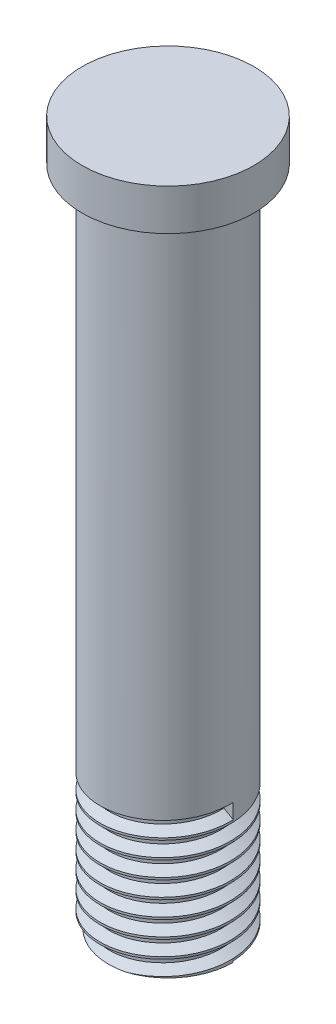
SolidWorks part; units mm, degrees
ref_plane "Front Plane" through (0, 0, 0) normal (0, 0, 1) x (1, 0, 0)
ref_plane "Top Plane" through (0, 0, 0) normal (0, 1, 0) x (1, 0, 0)
ref_plane "Right Plane" through (0, 0, 0) normal (1, 0, 0) x (0, 0, -1)
sketch "Sketch1" plane through (0, 0, 0) normal (0, 1, 0) x (1, 0, 0)
  circle A0 centre (0, 0) radius 4.75
  dimension "D1" = 9.5
extrude "Boss-Extrude1" add sketch "Sketch1" along normal blind 48
sketch "Sketch2" plane through (0, 48, 0) normal (0, 1, 0) x (1, 0, 0)
  circle A0 centre (0, 0) radius 6.25
  circle A1 centre (0, 0) radius 4.75 construction
  dimension "D1" = 1.5
extrude "Boss-Extrude2" add sketch "Sketch2" along normal blind 3
thread "Thread1" pitch 1.25 method cut profile "Thread Profile1" start angle 0, offset 1, length 10, pitch 1.25, diameter 9.5
ref_plane "Plane1" through (4.75, -1, 0) normal (0, 0, 1) x (1, 0, 0)
sketch "Thread Profile1" plane through (4.75, -1, 0) normal (0, 0, 1) x (1, 0, 0)
  line L0 (0, 0) -> (0, 1.25) construction
  line L11 (0, 0) -> (0, 1.0937)
  line L12 (0, 1.0937) -> (-0.6766, 0.7031)
  line L13 (-0.6766, 0.7031) -> (-0.6766, 0.3906)
  line L15 (-0.6766, 0.3906) -> (0, 0)
  line L17 (-0.6766, 0.5469) -> (0, 0.5469) construction
  point P2 (0, 0)
  dimension "Pitch" = 1.25
  dimension "Profile_Angle" = 60
  dimension "Profile_Land" = 0.3125
  dimension "Profile_Height" = 0.6766
